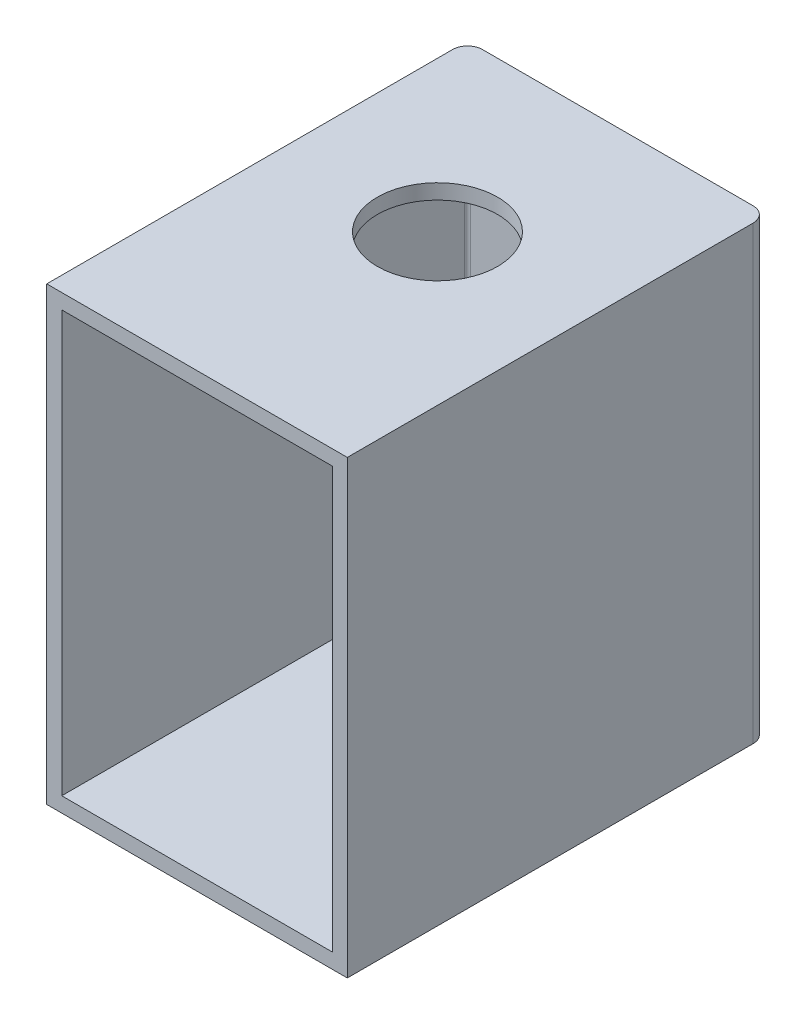
SolidWorks part; units mm, degrees
material "Alloy Steel"
ref_plane "Front Plane" through (0, 0, 0) normal (0, 0, 1) x (1, 0, 0)
ref_plane "Top Plane" through (0, 0, 0) normal (0, 1, 0) x (1, 0, 0)
ref_plane "Right Plane" through (0, 0, 0) normal (1, 0, 0) x (0, 0, -1)
sketch "MainBodyS" plane through (0, 0, 0) normal (0, 1, 0) x (1, 0, 0)
  line L1 (-10, 14) -> (10, 14)
  line L2 (-10, 14) -> (-10, -14)
  line L3 (-10, -14) -> (10, -14)
  line L4 (10, 14) -> (10, -14)
  line L5 (-10, 14) -> (10, -14) construction
  line L6 (-10, -14) -> (10, 14) construction
  point P0 (0, 0)
  dimension "D1" = 20
  dimension "D2" = 28
extrude "MAIN BODY" add sketch "MainBodyS" along normal mid plane 30
fillet "MB FILLET" radius 1 2 edges at (-10, 0, -14) (10, 0, -14)
shell "SHELL MB" thickness 1 removed face at (0, 0, 14)
sketch "TopBoreS" plane through (0, 15, 0) normal (0, 1, 0) x (1, 0, 0)
  line L0 (0, 0) -> (0, 2) construction
  line L1 (9, 14) -> (-9, 14) construction
  circle A0 centre (0, 2) radius 4
  dimension "D1" = 8
  dimension "D2" = 12
extrude "TOP BORE" cut sketch "TopBoreS" against normal up to next
sketch "BottomBoreS" plane through (0, -14, 0) normal (0, 1, 0) x (1, 0, 0)
  circle A0 centre (0, 2) radius 4.5
  circle A1 centre (0, 2) radius 4 construction
  dimension "D1" = 0.5
extrude "BOTTOM BORE" cut sketch "BottomBoreS" against normal through all
fillet "MB INNER FILLET" radius 0.2 2 edges at (9, 0, -13) (-9, 0, -13)
